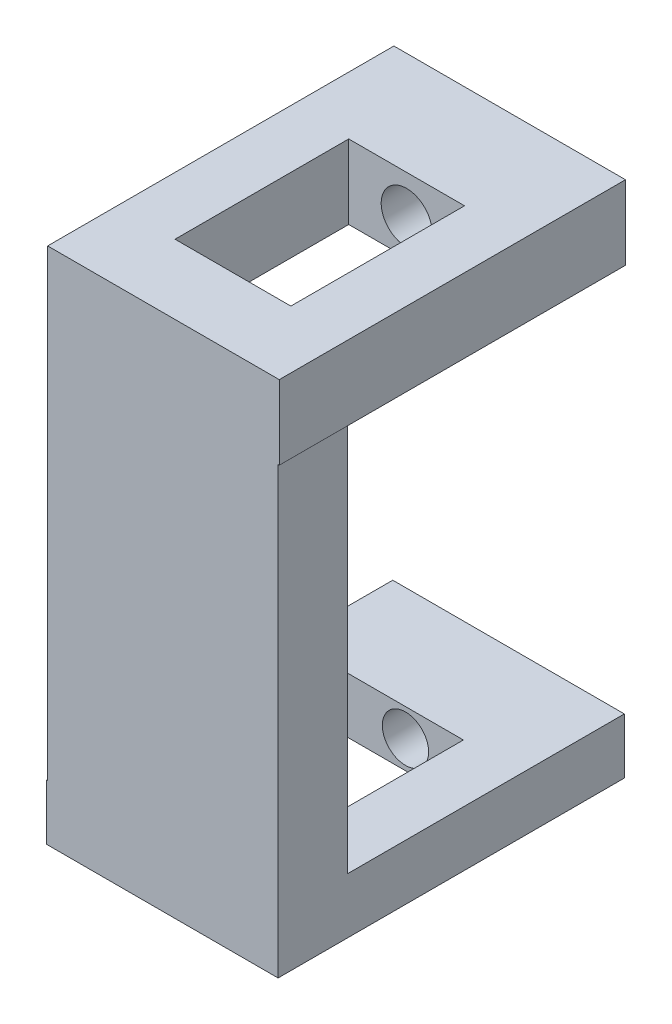
SolidWorks part; units mm, degrees
ref_plane "Płaszczyzna przednia" through (0, 0, 0) normal (0, 0, 1) x (1, 0, 0)
ref_plane "Płaszczyzna górna" through (0, 0, 0) normal (0, 1, 0) x (1, 0, 0)
ref_plane "Płaszczyzna prawa" through (0, 0, 0) normal (1, 0, 0) x (0, 0, -1)
sketch "Szkic2" plane through (0, 0, 158.8329) normal (0, 0, 1) x (1, 0, 0)
  line L0 (-31.9233, -22.4743) -> (2.0767, -22.4743) construction
  line L1 (-19.9235, -0.0745) -> (-9.9235, -0.0745)
  line L2 (-19.9235, -0.0745) -> (-19.9235, -3.2745)
  line L3 (-19.9235, -3.2745) -> (-9.9235, -3.2745)
  line L4 (-9.9235, -0.0745) -> (-9.9235, -3.2745)
  line L5 (-19.9733, -20.0743) -> (-9.9733, -20.0743)
  line L6 (-19.9733, -20.0743) -> (-19.9733, -22.4743)
  line L7 (-19.9733, -22.4743) -> (-9.9733, -22.4743)
  line L8 (-9.9733, -20.0743) -> (-9.9733, -22.4743)
  circle A0 centre (-14.9733, -21.2743) radius 1 construction
  circle A1 centre (-14.9235, -1.7745) radius 1.1 construction
  circle A2 centre (-14.9733, -21.2743) radius 1
  circle A3 centre (-14.9235, -1.7745) radius 1.1
  dimension "D1" = 10
  dimension "D2" = 5
  dimension "D3" = 1.2
  dimension "D4" = 10
  dimension "D5" = 5
  dimension "D6" = 1.7
  dimension "D7" = 1.5
extrude "Dodanie-wyciągnięcie1" add sketch "Szkic2" along normal blind 14.95
sketch "Szkic3" plane through (0, 0, 173.7829) normal (0, 0, 1) x (1, 0, 0)
  line L0 (-9.9235, -0.0745) -> (-19.9235, -0.0745) construction
  line L1 (-12.4235, -0.0745) -> (-17.4235, -0.0745)
  line L2 (-12.4235, -0.0745) -> (-12.4235, -3.2745)
  line L3 (-12.4235, -3.2745) -> (-17.4235, -3.2745)
  line L4 (-17.4235, -0.0745) -> (-17.4235, -3.2745)
  line L5 (-19.9235, -3.2745) -> (-9.9235, -3.2745) construction
  line L6 (-9.9733, -20.0743) -> (-19.9733, -20.0743) construction
  line L7 (-12.4733, -20.0743) -> (-17.4733, -20.0743)
  line L8 (-12.4733, -20.0743) -> (-12.4733, -22.4743)
  line L9 (-12.4733, -22.4743) -> (-17.4733, -22.4743)
  line L10 (-17.4733, -20.0743) -> (-17.4733, -22.4743)
  line L11 (-19.9733, -22.4743) -> (-9.9733, -22.4743) construction
  line L12 (-9.9733, -22.4743) -> (-9.9733, -20.0743) construction
  line L13 (-19.9733, -20.0743) -> (-19.9733, -22.4743) construction
  line L14 (-19.9235, -0.0745) -> (-19.9235, -3.2745) construction
  line L15 (-9.9235, -3.2745) -> (-9.9235, -0.0745) construction
  point P22 (-19.9235, -1.6745)
  dimension "D1" = 2.5
  dimension "D2" = 2.5
  dimension "D3" = 2.5
  dimension "D4" = 2.5
extrude "Wytnij-wyciągnięcie1" cut sketch "Szkic3" against normal blind 10.5
sketch "Szkic4" plane through (0, 0, 173.7829) normal (0, 0, 1) x (1, 0, 0)
  line L1 (-19.9235, -0.0745) -> (-9.9733, -0.0745)
  line L2 (-19.9235, -0.0745) -> (-19.9235, -22.4743)
  line L3 (-19.9235, -22.4743) -> (-9.9733, -22.4743)
  line L4 (-9.9733, -0.0745) -> (-9.9733, -22.4743)
extrude "Dodanie-wyciągnięcie2" add sketch "Szkic4" against normal blind 3
